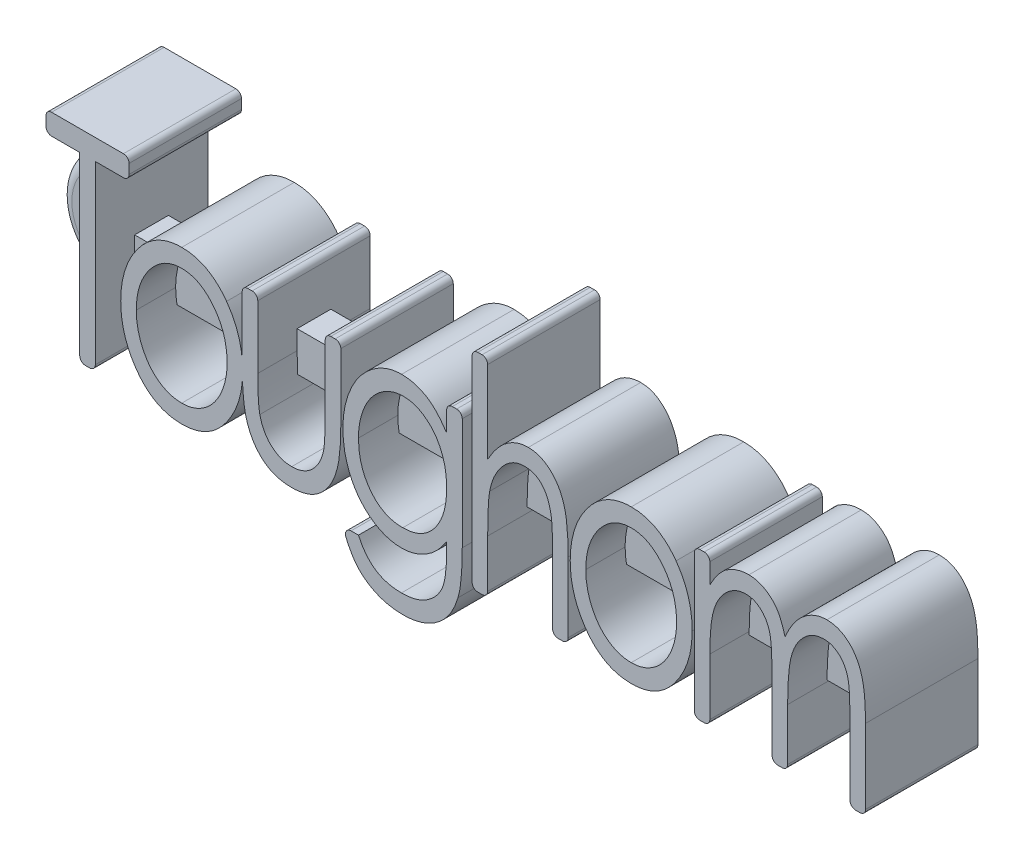
SolidWorks part; units mm, degrees
ref_plane "Front Plane" through (0, 0, 0) normal (0, 0, 1) x (1, 0, 0)
ref_plane "Top Plane" through (0, 0, 0) normal (0, 1, 0) x (1, 0, 0)
ref_plane "Right Plane" through (0, 0, 0) normal (1, 0, 0) x (0, 0, -1)
sketch "Sketch1" plane through (0, 0, 0) normal (0, 0, 1) x (1, 0, 0)
  line L1 (-34.1, 1.75) -> (34.1, 1.75)
  line L2 (-34.1, 1.75) -> (-34.1, -1.75)
  line L3 (-34.1, -1.75) -> (34.1, -1.75)
  line L4 (34.1, 1.75) -> (34.1, -1.75)
  line L5 (-34.1, 1.75) -> (34.1, -1.75) construction
  line L6 (-34.1, -1.75) -> (34.1, 1.75) construction
  point P0 (0, 0)
  dimension "D1" = 3.5
  dimension "D2" = 68.2
extrude "Boss-Extrude1" add sketch "Sketch1" along normal mid plane 3
sketch "Sketch2" plane through (0, 0, 0) normal (0, 0, 1) x (1, 0, 0)
  line L0 (0, 0) -> (0, -7) construction
  line L1 (-79.262, -7) -> (76.9306, -7) construction
  text T0 "Toughom" font "Century Gothic" height 18
  point P4 (0, 0)
  point P10 (0, -7)
  dimension "D1" = 7
extrude "Boss-Extrude2" add sketch "Sketch2" along normal mid plane 10
sketch "Sketch3" plane through (0, 0, 0) normal (0, 0, 1) x (1, 0, 0)
  line L0 (-35.1811, -7) -> (-35.1811, 9.1538) construction
  line L1 (-35.1811, 6.7347) -> (-35.1811, 5.0347)
  line L2 (-35.1811, -1.9653) -> (-35.1811, -3.6653)
  arc A0 (-35.1811, 6.7347) -> (-35.1811, -3.6653) centre (-35.1811, 1.5347) ccw
  arc A1 (-35.1811, 5.0347) -> (-35.1811, -1.9653) centre (-35.1811, 1.5347) ccw
  dimension "D1" = 5.2
  dimension "D2" = 3.5
extrude "Boss-Extrude3" add sketch "Sketch3" along normal mid plane 3
fillet "Fillet1" radius 1 8 edges at (-35.1811, 5.8847, 1.5) (-35.1811, 5.8847, -1.5) (-35.1811, -2.8153, 1.5) (-35.1811, -2.8153, -1.5) (-35.1811, 6.7347, 0) (-40.3811, 1.5347, 1.5) (-35.1811, -3.6653, 0) (-40.3811, 1.5347, -1.5)
fillet "Fillet2" radius 0.5 27 edges at (34.6958, -7, 0) (33.3112, -7, 0) (27.7727, -7, 0) (26.3881, -7, 0) (20.8497, -7, 0) (19.465, -7, 0) (20.8497, 6.1538, 0) (19.465, 6.1538, 0) (8.2497, -7, 0) (6.865, -7, 0) (1.0958, -7, 0) (-0.2888, -7, 0) (1.0958, 11.4615, 0) (-0.2888, 11.4615, 0) (-11.7811, -7.9231, 0) (-1.1657, 6.1538, 0) (-2.5503, 6.1538, 0) (-11.9657, 6.1538, 0) (-13.3503, 6.1538, 0) (-19.3503, 6.1538, 0) (-20.735, 6.1538, 0) (-33.7965, -7, 0) (-35.1811, -7, 0) (-30.7965, 9.1538, 0) (-30.7965, 11, 0) (-38.1811, 9.1538, 0) (-38.1811, 11, 0)
fillet "Fillet4" radius 1 2 edges at (-35.1811, -1.9653, 0) (-35.1811, 5.0347, 0)
